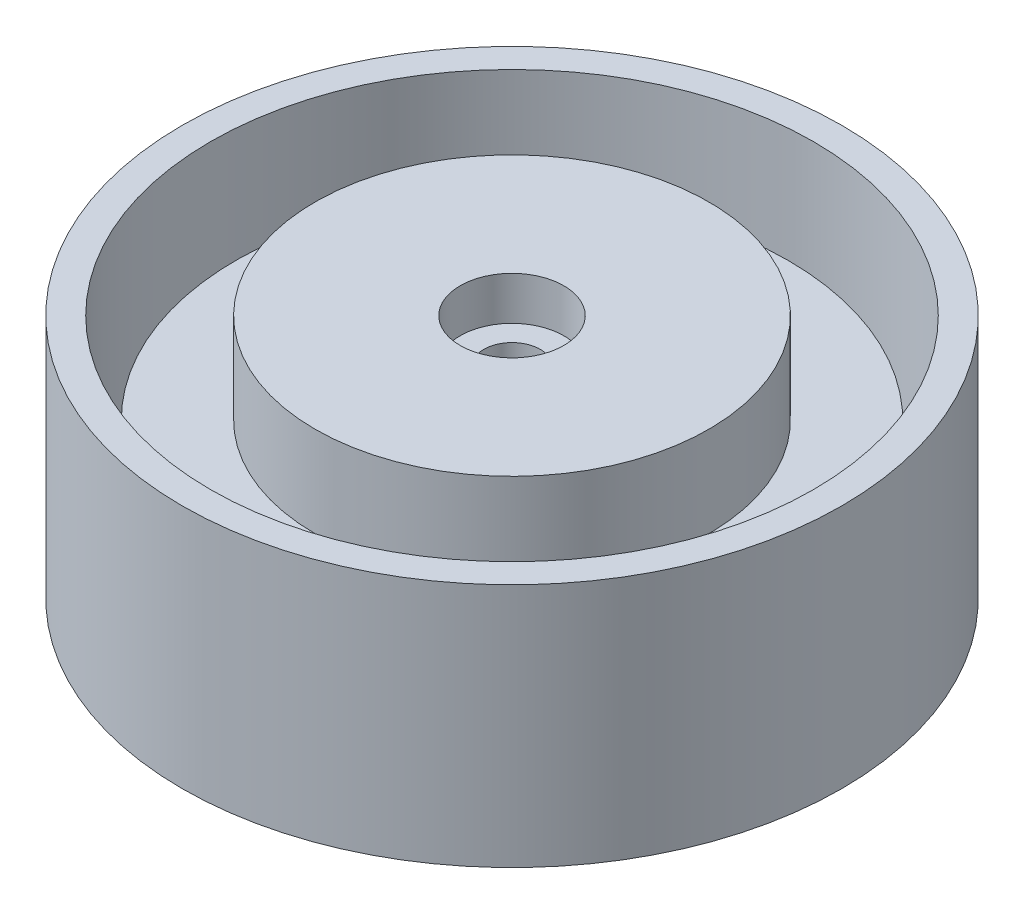
SolidWorks part; units mm, degrees
material "ColorFabb woodFILL"
ref_plane "Front Plane" through (0, 0, 0) normal (0, 0, 1) x (1, 0, 0)
ref_plane "Top Plane" through (0, 0, 0) normal (0, 1, 0) x (1, 0, 0)
ref_plane "Right Plane" through (0, 0, 0) normal (1, 0, 0) x (0, 0, -1)
sketch "Volume Knob" plane through (0, 0, 0) normal (0, 1, 0) x (1, 0, 0)
  line L1 (2.5981, 1.5) -> (-2.5981, 1.5)
  circle A0 centre (0, 0) radius 35
  circle A1 centre (0, 0) radius 20.9
  circle A2 centre (0, 0) radius 32
  circle A3 centre (0, 0) radius 3
  circle A4 centre (0, 0) radius 5.5
  circle A5 centre (0, 0) radius 27.5
  circle A6 centre (0, 0) radius 29.33
  point P11 (0, 1)
  point P12 (0, 1.5)
extrude "Knob Top" add sketch "Volume Knob" along normal blind 3.5 contours A0
extrude "Knob Walls" add sketch "Volume Knob<3>" along normal blind 26 contours A0 | A2
sketch "Volume Knob<3>" plane through (0, 0, 0) normal (0, 1, 0) x (1, 0, 0) same geometry as "Volume Knob"
extrude "Knob Shaft Keyway" add sketch "Volume Knob<4>" along normal blind 10 from surface contours L1 A3 region at (0, 0, -2.1151) starting at face at (0, 3.5, 32)
sketch "Volume Knob<4>" plane through (0, 0, 0) normal (0, 1, 0) x (1, 0, 0) same geometry as "Volume Knob"
extrude "Knob Damepning Extension (top)" add sketch "Volume Knob<8>" along normal blind 12.9 from surface contours A6 | A3 starting at face at (0, 3.5, 32)
sketch "Volume Knob<8>" plane through (0, 0, 0) normal (0, 1, 0) x (1, 0, 0) same geometry as "Volume Knob"
extrude "Knob Shaft Support" add sketch "Volume Knob<11>" along normal blind 5 from surface contours A1 | A3 starting at face at (0, 16.4, 29.33)
sketch "Volume Knob<11>" plane through (0, 0, 0) normal (0, 1, 0) x (1, 0, 0) same geometry as "Volume Knob"
extrude "Knob Damepning Extension (side)" add sketch "Volume Knob<12>" along normal up to surface (26 mm away) from surface contours A1 | A4 up to face at (0, 26, 35) starting at face at (0, 21.4, 20.9)
sketch "Volume Knob<12>" plane through (0, 0, 0) normal (0, 1, 0) x (1, 0, 0) same geometry as "Volume Knob"
